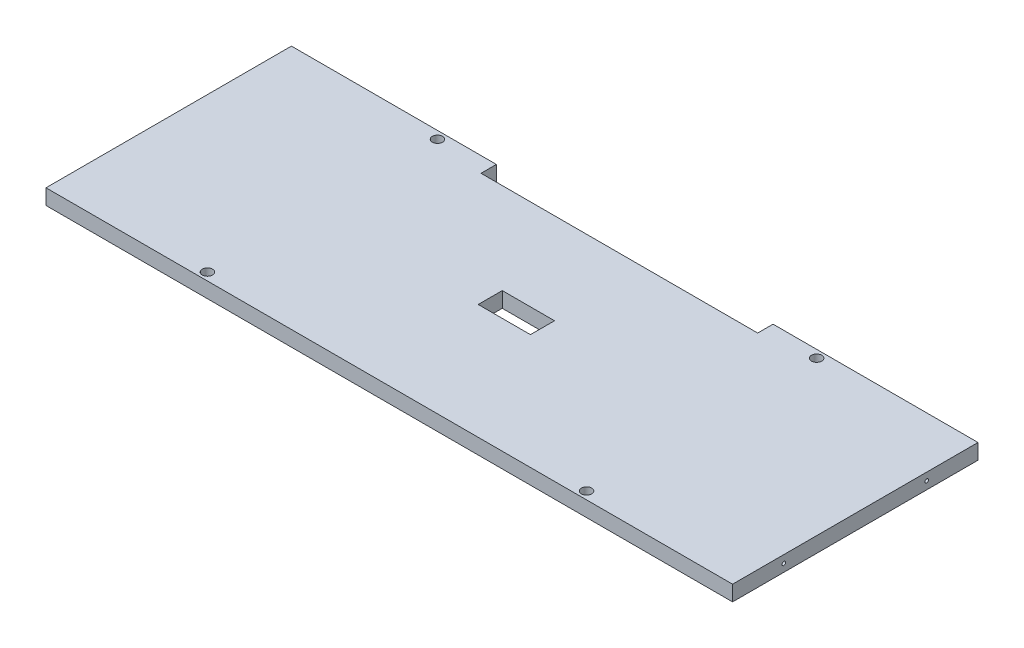
SolidWorks part; units mm, degrees
ref_plane "前视基准面" through (0, 0, 0) normal (0, 0, 1) x (1, 0, 0)
ref_plane "上视基准面" through (0, 0, 0) normal (0, 1, 0) x (1, 0, 0)
ref_plane "右视基准面" through (0, 0, 0) normal (1, 0, 0) x (0, 0, -1)
other "Configuration Table"
sketch "草图1" plane through (0, 0, 0) normal (0, 0, 1) x (1, 0, 0)
  line L61 (-67, 1.5) -> (67, 1.5)
  line L62 (-67, 1.5) -> (-67, -1.5)
  line L63 (-67, -1.5) -> (67, -1.5)
  line L64 (67, 1.5) -> (67, -1.5)
  point P4 (0, 1.5)
  point P5 (-67, 0)
  dimension "D1" = 3
  dimension "D2" = 134
extrude "凸台-拉伸1" add sketch "草图1" along normal blind 47.9
sketch "草图4" plane through (0, 1.5, 0) normal (0, 1, 0) x (1, 0, 0)
  line L0 (-37, -46.4) -> (37, -46.4)
  line L1 (-67, -47.9) -> (-67, 0) construction
  line L2 (67, -47.9) -> (-67, -47.9) construction
  line L3 (-5.1, -23.1) -> (5.1, -23.1)
  line L4 (-5.1, -20.75) -> (5.1, -20.75)
  line L5 (-5.1, -20.75) -> (-5.1, -25.45)
  line L6 (-5.1, -25.45) -> (5.1, -25.45)
  line L7 (5.1, -20.75) -> (5.1, -25.45)
  line L9 (-67, 0) -> (67, 0) construction
  line L10 (27, 0) -> (-27, 0)
  line L11 (27, 0) -> (27, -3)
  line L12 (27, -3) -> (-27, -3)
  line L13 (-27, 0) -> (-27, -3)
  line L14 (67, 0) -> (-67, 0) construction
  circle A0 centre (-37, -46.4) radius 0.7
  circle A1 centre (37, -46.4) radius 0.7
  circle A2 centre (-37, -46.4) radius 1
  circle A3 centre (37, -46.4) radius 1
  circle A5 centre (-37, -1.5) radius 0.7
  circle A6 centre (37, -1.5) radius 0.7
  circle A7 centre (37, -1.5) radius 1
  circle A8 centre (-37, -1.5) radius 1
  point P6 (0, -46.4)
  point P16 (0, -20.75)
  point P31 (0, 0)
  point P34 (0, 0)
  point P35 (0, 0)
  dimension "D1" = 1.4
  dimension "D2" = 2
  dimension "D3" = 30
  dimension "D4" = 1.5
  dimension "D5" = 10.2
  dimension "D6" = 4.7
  dimension "D7" = 24.8
  dimension "D8" = 3
  dimension "D9" = 54
  dimension "D10" = 1.5
extrude "切除-拉伸1" cut sketch "草图4" against normal through all contours A1 | A0 | L6 L7 L4 L5 | L12 L13 L10 L11 | A5 | A6
extrude "切除-拉伸2" cut sketch "草图4<3>" against normal blind 1.5 contours A2 | A3 | A7 | A8
sketch "草图4<3>" plane through (0, 1.5, 0) normal (0, 1, 0) x (1, 0, 0) same geometry as "草图4"
sketch "草图5" plane through (0, -1.5, 0) normal (0, -1, 0) x (1, 0, 0)
  circle A0 centre (42.3, 22.35) radius 0.35
  circle A1 centre (-42.3, 22.35) radius 0.35
  point P6 (0, 0)
  point P7 (0, 0)
  dimension "D1" = 0.7
extrude "切除-拉伸3" cut sketch "草图5" against normal blind 1.5 contours A0 | A1
sketch "草图6" plane through (0, 0, 3) normal (0, 0, -1) x (-1, 0, 0)
  circle A2 centre (0, 0) radius 0.35
  dimension "D4" = 0.7
extrude "切除-拉伸4" cut sketch "草图6" against normal blind 1.5 contours A2
sketch "草图7" plane through (67, 0, 0) normal (1, 0, 0) x (0, 0, -1)
  line L0 (-10, 0) -> (0, 0)
  line L1 (-37.9, 0) -> (-47.9, 0)
  line L2 (-47.9, -1.5) -> (-47.9, 1.5) construction
  circle A0 centre (-10, 0) radius 0.35
  circle A1 centre (-37.9, 0) radius 0.35
  point P4 (-36.25, 0)
  dimension "D2" = 0.7
  dimension "D1" = 10
extrude "切除-拉伸5" cut sketch "草图7" against normal blind 1.5 contours A0 | A1
extrude "切除-拉伸6" cut sketch "草图7<3>" along normal blind 1.5 from surface contours A0 | A1 starting at face at (-67, 0, 23.95)
sketch "草图7<3>" plane through (67, 0, 0) normal (1, 0, 0) x (0, 0, -1) same geometry as "草图7"
